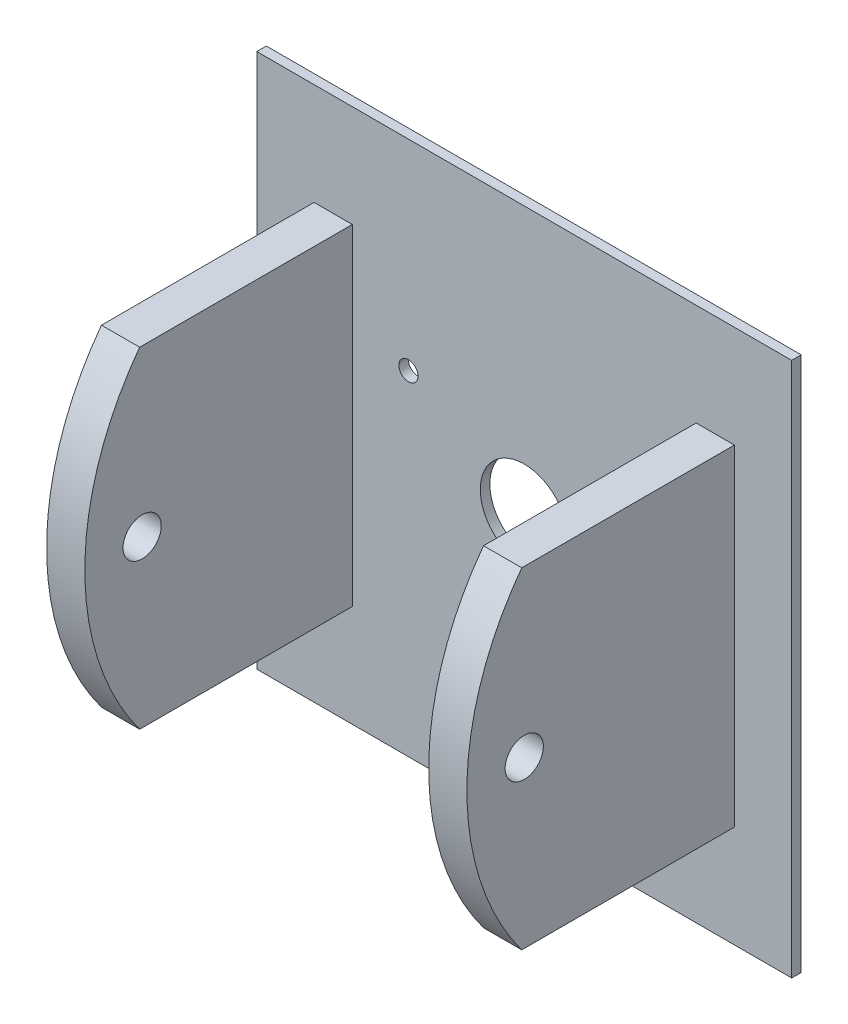
SolidWorks part; units mm, degrees
ref_plane "Front Plane" through (0, 0, 0) normal (0, 0, 1) x (1, 0, 0)
ref_plane "Top Plane" through (0, 0, 0) normal (0, 1, 0) x (1, 0, 0)
ref_plane "Right Plane" through (0, 0, 0) normal (1, 0, 0) x (0, 0, -1)
sketch "Sketch1" plane through (0, 0, 0) normal (0, 0, 1) x (1, 0, 0)
  line L1 (-88.9, 88.9) -> (88.9, 88.9)
  line L2 (-88.9, 88.9) -> (-88.9, -88.9)
  line L3 (-88.9, -88.9) -> (88.9, -88.9)
  line L4 (88.9, 88.9) -> (88.9, -88.9)
  line L5 (-88.9, 88.9) -> (88.9, -88.9) construction
  line L6 (-88.9, -88.9) -> (88.9, 88.9) construction
  circle A0 centre (0, 0) radius 14.605
  point P0 (0, 0)
  dimension "D2" = 29.21
  dimension "D1" = 177.8
extrude "Boss-Extrude1" add sketch "Sketch1" along normal blind 3.175
sketch "Sketch2" plane through (0, 0, 3.175) normal (0, 0, 1) x (1, 0, 0)
  line L0 (-88.9, 88.9) -> (-88.9, -88.9) construction
  line L1 (1.8142, 0) -> (50001.8142, 0) construction
  line L2 (0, 88.9) -> (0, 0) construction
  line L3 (0, 88.9) -> (-76.9897, -44.45) construction
  line L4 (-76.9897, -44.45) -> (76.9897, -44.45) construction
  line L5 (76.9897, -44.45) -> (0, 88.9) construction
  line L6 (-76.9897, -44.45) -> (0, 0) construction
  line L7 (0, 0) -> (76.9897, 44.45) construction
  line L8 (76.9897, -44.45) -> (0, 0) construction
  line L9 (0, 0) -> (-76.9897, 44.45) construction
  line L10 (0, 0) -> (0, -88.9) construction
  line L11 (-69.85, 54.9926) -> (-69.85, -54.9926)
  line L12 (69.85, -54.9926) -> (69.85, 54.9926)
  line L13 (-57.15, 54.9926) -> (-57.15, -54.9926)
  line L14 (57.15, -54.9926) -> (57.15, 54.9926)
  line L15 (88.9, -88.9) -> (88.9, 88.9)
  line L16 (88.9, 88.9) -> (-88.9, 88.9)
  line L17 (-88.9, 88.9) -> (-88.9, -88.9)
  line L18 (-88.9, -88.9) -> (88.9, -88.9)
  line L19 (88.9, -88.9) -> (88.9, 88.9)
  line L20 (88.9, 88.9) -> (-88.9, 88.9)
  line L21 (-88.9, 88.9) -> (-88.9, -88.9)
  line L22 (-88.9, -88.9) -> (88.9, -88.9)
  line L23 (-69.85, 54.9926) -> (-57.15, 54.9926)
  line L24 (-69.85, -54.9926) -> (-57.15, -54.9926)
  line L25 (69.85, -54.9926) -> (57.15, -54.9926)
  line L26 (69.85, 54.9926) -> (57.15, 54.9926)
  line L28 (-69.85, 88.9) -> (-69.85, -88.9) construction
  line L29 (-57.15, 88.9) -> (-57.15, -88.9) construction
  line L30 (57.15, -88.9) -> (57.15, 88.9) construction
  line L31 (69.85, -88.9) -> (69.85, 88.9) construction
  circle A0 centre (0, 0) radius 88.9
  circle A1 centre (-38.4948, 22.225) radius 3.175
  circle A2 centre (0, -44.45) radius 3.175
  circle A3 centre (38.4948, 22.225) radius 3.175
  point P39 (0, 0)
  point P40 (0, 0)
  point P41 (0, 0)
  point P42 (-57.15, -43.7915)
  dimension "D1" = 6.35
  dimension "D2" = 0
  dimension "D3" = 19.05
  dimension "D4" = 12.7
extrude "Cut-Extrude1" cut sketch "Sketch2" against normal through all contours A1 | A3 | A2 region at (-38.4948, 22.225, 3.175) region at (0, -44.45, 3.175) region at (38.4948, 22.225, 3.175)
extrude "Boss-Extrude2" add sketch "Sketch2<3>" along normal blind 88.9 contours L11 L24 L13 L23 | L14 L26 L12 L25 region at (-63.5, 0, 3.175)
sketch "Sketch2<3>" plane through (0, 0, 3.175) normal (0, 0, 1) x (1, 0, 0) same geometry as "Sketch2"
sketch "Sketch3" plane through (-69.85, 0, 0) normal (-1, 0, 0) x (0, 0, 1)
  line L0 (0, 0) -> (92.075, 0) construction
  line L4 (3.175, 54.9926) -> (3.175, -54.9926)
  line L5 (3.175, -54.9926) -> (92.075, -54.9926)
  line L6 (92.075, -54.9926) -> (92.075, 54.9926)
  line L7 (92.075, 54.9926) -> (3.175, 54.9926)
  line L8 (3.175, 54.9926) -> (3.175, -54.9926)
  line L9 (3.175, -54.9926) -> (92.075, -54.9926)
  line L10 (92.075, -54.9926) -> (92.075, 54.9926)
  line L11 (92.075, 54.9926) -> (3.175, 54.9926)
  arc A0 (73.8486, -54.9926) -> (73.8486, 54.9926) centre (0, 0) ccw
  circle A1 centre (73.025, 0) radius 6.35
  line M8 (92.075, -54.9926) -> (92.075, 54.9926)
  line M9 (92.075, 54.9926) -> (3.175, 54.9926)
  dimension "D3" = 12.7
  dimension "D2" = 19.05
  dimension "D1" = 0
extrude "Cut-Extrude2" cut sketch "Sketch3" against normal through all contours A0 L10 M9 | A0 L9 M8 | L0 A1 | A1 L0 region at (-69.85, -2.695, 73.025) region at (-69.85, 2.695, 73.025) region at (-69.85, 41.5315, 86.7143) region at (-69.85, -41.5315, 86.7143)
